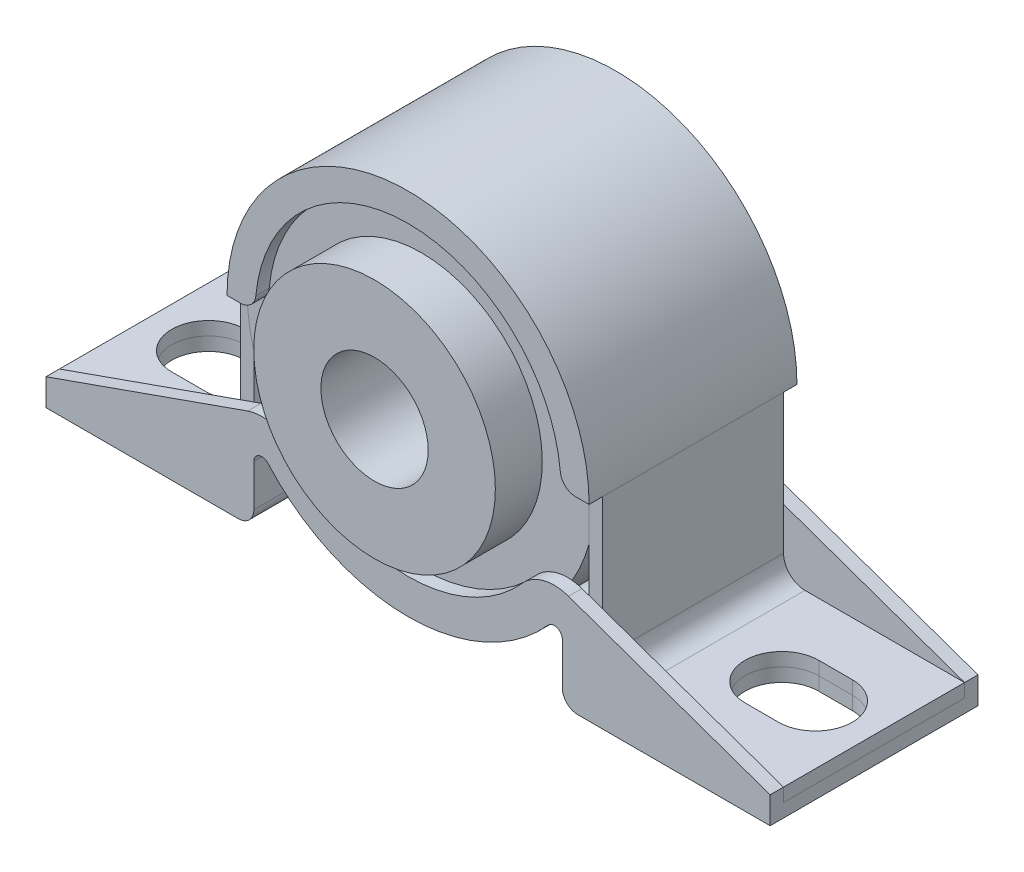
SolidWorks part; units mm, degrees
ref_plane "Front" through (0, 0, 0) normal (0, 0, 1) x (1, 0, 0)
ref_plane "Top" through (0, 0, 0) normal (0, 1, 0) x (1, 0, 0)
ref_plane "Right" through (0, 0, 0) normal (1, 0, 0) x (0, 0, -1)
sketch "Sketch1" plane through (0, 0, 0) normal (0, 0, 1) x (1, 0, 0)
  line L1 (-23.9712, -19.05) -> (-42.8625, -19.05) construction
  line L2 (-42.8625, -19.05) -> (-42.8625, -22.225) construction
  line L3 (-42.8625, -22.225) -> (42.8625, -22.225) construction
  line L6 (0, 0) -> (0, -22.225) construction
  line L9 (42.8625, -22.225) -> (42.8625, -19.05) construction
  line L10 (42.8625, -19.05) -> (23.9713, -19.05) construction
  line L12 (-21.4313, 0) -> (-21.4312, -16.51) construction
  line L13 (-42.8625, -20.6375) -> (-19.8438, -20.6375)
  line L14 (21.4313, 0) -> (21.4313, -16.51) construction
  line L15 (-19.8438, -20.6375) -> (-19.8438, -15.42)
  line L16 (19.8438, -15.42) -> (19.8438, -20.6375)
  line L17 (19.8438, -20.6375) -> (42.8625, -20.6375)
  circle A0 centre (0, 0) radius 6.35 construction
  circle A1 centre (0, 0) radius 14.3002 construction
  arc A2 (21.4313, 0) -> (-21.4313, 0) centre (0, 0) ccw construction
  arc A5 (-21.4312, -16.51) -> (-23.9712, -19.05) centre (-23.9712, -16.51) cw construction
  arc A6 (21.4313, -16.51) -> (23.9713, -19.05) centre (23.9713, -16.51) ccw construction
  arc A7 (-19.8438, -15.42) -> (-15.4074, -13.7301) centre (-17.3038, -15.42) cw
  arc A8 (-15.4074, -13.7301) -> (15.4074, -13.7301) centre (0, 0) ccw
  arc A9 (15.4074, -13.7301) -> (19.8438, -15.42) centre (17.3038, -15.42) cw
  dimension "Shaft Dia" = 12.7
  dimension "K" = 28.6004
  dimension "D1" = 2.54
  dimension "w" = 43.6562
  dimension "h" = 22.225
  dimension "g" = 3.175
  dimension "a" = 85.725
  dimension "D2" = 1.5875
extrude "Extrude-Thin2" add sketch "Sketch1" along normal mid plane 24.6062 thin thin type one direction wall 1.5875
sketch "Sketch4" plane through (0, 0, 12.3031) normal (0, 0, 1) x (1, 0, 0)
  line L0 (-42.8625, -19.05) -> (-18.9938, -10.6294)
  line L1 (18.9938, -10.6294) -> (42.8625, -19.05)
  line L2 (-23.9712, -19.05) -> (-42.8625, -19.05) construction
  line L3 (42.8625, -19.05) -> (23.9713, -19.05) construction
  line L10 (20.0978, -22.225) -> (42.8625, -22.225)
  line L11 (42.8625, -22.225) -> (42.8625, -20.6375)
  line L12 (42.8625, -20.6375) -> (20.0978, -20.6375)
  line L13 (19.8438, -20.3835) -> (19.8438, -15.42)
  line L14 (-19.8438, -15.42) -> (-19.8438, -20.3835)
  line L15 (-20.0978, -20.6375) -> (-42.8625, -20.6375)
  line L16 (-42.8625, -20.6375) -> (-42.8625, -22.225)
  line L17 (-42.8625, -22.225) -> (-20.0978, -22.225)
  line L18 (-18.2563, -20.3835) -> (-18.2563, -15.42)
  line L19 (18.2563, -15.42) -> (18.2563, -20.3835)
  line L20 (20.0978, -22.225) -> (42.8625, -22.225)
  line L21 (42.8625, -22.225) -> (42.8625, -19.05)
  line L26 (-42.8625, -19.05) -> (-42.8625, -22.225)
  line L27 (-42.8625, -22.225) -> (-20.0978, -22.225)
  line L28 (-18.2563, -20.3835) -> (-18.2563, -15.42)
  line L29 (18.2563, -15.42) -> (18.2563, -20.3835)
  arc A0 (-13.5111, -12.0403) -> (-18.9938, -10.6294) centre (-17.3038, -15.42) ccw
  arc A1 (18.9938, -10.6294) -> (13.5111, -12.0403) centre (17.3038, -15.42) ccw
  arc A2 (-13.5111, -12.0403) -> (13.5111, -12.0403) centre (0, 0) ccw
  arc A10 (19.8438, -20.3835) -> (20.0978, -20.6375) centre (20.0978, -20.3835) ccw
  arc A11 (19.8438, -15.42) -> (15.4074, -13.7301) centre (17.3038, -15.42) ccw
  arc A12 (-15.4074, -13.7301) -> (15.4074, -13.7301) centre (0, 0) ccw
  arc A13 (-15.4074, -13.7301) -> (-19.8438, -15.42) centre (-17.3038, -15.42) ccw
  arc A14 (-20.0978, -20.6375) -> (-19.8438, -20.3835) centre (-20.0978, -20.3835) ccw
  arc A15 (-20.0978, -22.225) -> (-18.2563, -20.3835) centre (-20.0978, -20.3835) ccw
  arc A17 (-16.5926, -14.7863) -> (16.5926, -14.7863) centre (0, 0) ccw
  arc A19 (18.2563, -20.3835) -> (20.0978, -22.225) centre (20.0978, -20.3835) ccw
  arc A21 (-16.5926, -14.7863) -> (-18.2563, -15.42) centre (-17.3038, -15.42) ccw
  arc A22 (-16.5926, -14.7863) -> (-18.2563, -15.42) centre (-17.3038, -15.42) ccw
  arc A23 (18.2563, -15.42) -> (16.5926, -14.7863) centre (17.3038, -15.42) ccw
  arc A24 (18.2563, -15.42) -> (16.5926, -14.7863) centre (17.3038, -15.42) ccw
  arc A25 (-20.0978, -22.225) -> (-18.2563, -20.3835) centre (-20.0978, -20.3835) ccw
  arc A27 (-16.5926, -14.7863) -> (16.5926, -14.7863) centre (0, 0) ccw
  arc A29 (18.2563, -20.3835) -> (20.0978, -22.225) centre (20.0978, -20.3835) ccw
  dimension "D2" = 5.08
  dimension "D1" = 0
extrude "Extrude1" add sketch "Sketch4" against normal blind 1.5875
mirror "Mirror1" about plane through (0, 0, 0) normal (0, 0, 1) of "Extrude1"
sketch "Sketch5" plane through (0, 0, 0) normal (0, 0, 1) x (1, 0, 0)
  line L0 (42.8625, -19.05) -> (23.9713, -19.05) construction
  line L1 (21.4313, 0) -> (21.4313, -16.51) construction
  line L2 (-21.4313, 0) -> (-21.4312, -16.51) construction
  line L3 (-23.9712, -19.05) -> (-42.8625, -19.05) construction
  line L4 (42.8625, -19.05) -> (23.9713, -19.05)
  line L5 (21.4313, 0) -> (21.4313, -16.51)
  line L6 (-21.4313, 0) -> (-21.4312, -16.51)
  line L7 (-23.9712, -19.05) -> (-42.8625, -19.05)
  arc A0 (21.4313, -16.51) -> (23.9713, -19.05) centre (23.9713, -16.51) ccw construction
  arc A1 (21.4313, 0) -> (-21.4313, 0) centre (0, 0) ccw construction
  arc A2 (-23.9712, -19.05) -> (-21.4312, -16.51) centre (-23.9712, -16.51) ccw construction
  arc A3 (21.4313, -16.51) -> (23.9713, -19.05) centre (23.9713, -16.51) ccw
  arc A4 (21.4313, 0) -> (-21.4313, 0) centre (0, 0) ccw
  arc A5 (-23.9712, -19.05) -> (-21.4312, -16.51) centre (-23.9712, -16.51) ccw
extrude "Extrude-Thin3" add sketch "Sketch5" along normal up to surface (10.7156 mm away) and the other way up to surface (10.7156 mm away) separate body thin up to face at (0, -17.0875, 10.7156) other way up to face at (0, -17.0875, -10.7156) thin type one direction reverse wall 1.5875
sketch "Sketch6" plane through (0, 0, -10.7156) normal (0, 0, -1) x (-1, 0, 0)
  line L0 (-21.4313, 0) -> (21.4313, 0) construction
  line L1 (-19.8438, 0) -> (-21.4313, 0)
  line L2 (21.4313, 0) -> (19.8438, 0)
  arc A0 (21.4313, 0) -> (-21.4313, 0) centre (0, 0) ccw construction
  arc A1 (21.4313, 0) -> (-21.4313, 0) centre (0, 0) ccw
  arc A2 (-13.5111, -12.0403) -> (13.5111, -12.0403) centre (0, 0) ccw construction
  arc A3 (-13.5111, -12.0403) -> (18.0975, 0) centre (0, 0) ccw construction
  arc A4 (18.021, 1.6624) -> (-18.021, 1.6624) centre (0, 0) ccw
  arc A5 (19.8438, 0) -> (-19.8438, 0) centre (0, 0) ccw construction
  arc A6 (19.8438, 0) -> (-19.8438, 0) centre (0, 0) ccw construction
  arc A7 (-19.8438, 0) -> (-18.021, 1.6624) centre (-19.8438, 1.8305) ccw
  arc A8 (19.8438, 0) -> (18.021, 1.6624) centre (19.8438, 1.8305) cw
extrude "Extrude2" add sketch "Sketch6" along normal blind 1.5875
mirror "Mirror2" about plane through (0, 0, 0) normal (0, 0, 1) of "Extrude2"
sketch "Sketch7" plane through (0, 0, 0) normal (0, 0, 1) x (1, 0, 0)
  circle A0 centre (0, 0) radius 20.6375
  circle A1 centre (0, 0) radius 14.3002
  circle A2 centre (0, 0) radius 14.3002 construction
  arc A3 (-15.4074, -13.7301) -> (15.4074, -13.7301) centre (0, 0) ccw construction
extrude "Extrude3" add sketch "Sketch7" along normal up to surface (10.7156 mm away) and the other way up to surface (10.7156 mm away) separate body up to face at (0, -17.0875, 10.7156) other way up to face at (0, -17.0875, -10.7156)
ref_plane "Plane1" through (0, 0, 16.2719) normal (0, 0, -1) x (-1, 0, 0)
sketch "Sketch8" plane through (0, 0, 16.2719) normal (0, 0, 1) x (1, 0, 0)
  circle A0 centre (0, 0) radius 14.3002 construction
  circle A1 centre (0, 0) radius 6.35 construction
  circle A2 centre (0, 0) radius 14.3002
  circle A3 centre (0, 0) radius 6.35
extrude "Extrude4" add sketch "Sketch8" against normal blind 21.9989 separate body
sketch "Sketch3" plane through (0, 0, 0) normal (0, 1, 0) x (1, 0, 0)
  line L2 (-35.9172, 0) -> (-31.9484, 0) construction
  line L3 (-31.9484, 0) -> (0, 0) construction
  line L4 (0, 0) -> (31.9484, 0) construction
  line L5 (31.9484, 0) -> (35.9172, 0) construction
  line L6 (-35.9172, 4.3656) -> (-31.9484, 4.3656)
  line L7 (-35.9172, -4.3656) -> (-31.9484, -4.3656)
  line L8 (31.9484, -4.3656) -> (35.9172, -4.3656)
  line L9 (35.9172, 4.3656) -> (31.9484, 4.3656)
  line L10 (-33.9328, -4.3656) -> (-33.9328, 0) construction
  arc A0 (-35.9172, 4.3656) -> (-35.9172, -4.3656) centre (-35.9172, 0) ccw
  arc A1 (-31.9484, 4.3656) -> (-31.9484, -4.3656) centre (-31.9484, 0) cw
  arc A2 (31.9484, 4.3656) -> (31.9484, -4.3656) centre (31.9484, 0) ccw
  arc A3 (35.9172, 4.3656) -> (35.9172, -4.3656) centre (35.9172, 0) cw
  point P13 (33.9328, -4.3656)
  point P14 (-33.9328, -4.3656)
  dimension "D1" = 67.8656
  dimension "D2" = 12.7
  dimension "Slot Width" = 8.7312
extrude "Cut-Extrude1" cut sketch "Sketch3" against normal through all
sketch "Sketch9" plane through (0, 0, 0) normal (1, 0, 0) x (0, 0, -1)
  line L0 (5.7271, 0) -> (-16.2719, 0) construction
  line L3 (-16.2719, 6.35) -> (-16.2719, -6.35) construction
  line L4 (5.7271, -6.35) -> (5.7271, 6.35) construction
equation "\"D2@Sketch1\"=\"g@Sketch1\"/2"
equation "\"D5@Extrude-Thin2\"=\"g@Sketch1\"/2"
equation "\"D1@Extrude1\"=\"g@Sketch1\"/2"
equation "\"D5@Extrude-Thin3\" = \"g@Sketch1\"/2"
equation "\"D1@Extrude2\"=\"g@Sketch1\"/2"
